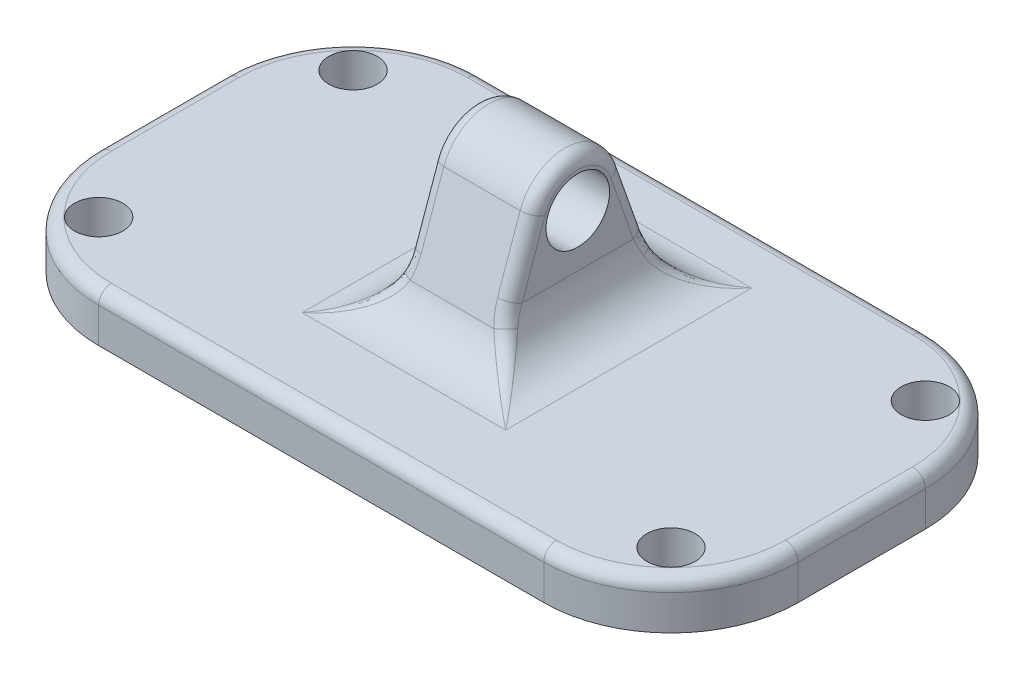
SolidWorks part; units mm, degrees
ref_plane "Front Plane" through (0, 0, 0) normal (0, 0, 1) x (1, 0, 0)
ref_plane "Top Plane" through (0, 0, 0) normal (0, 1, 0) x (1, 0, 0)
ref_plane "Right Plane" through (0, 0, 0) normal (1, 0, 0) x (0, 0, -1)
sketch "Sketch1" plane through (0, 0, 0) normal (0, 1, 0) x (1, 0, 0)
  line L0 (-57.15, 25.4) -> (57.15, 25.4) construction
  line L1 (-69.85, 38.1) -> (69.85, 38.1)
  line L2 (-69.85, 38.1) -> (-69.85, -38.1)
  line L3 (-69.85, -38.1) -> (69.85, -38.1)
  line L4 (69.85, 38.1) -> (69.85, -38.1)
  line L5 (-69.85, 38.1) -> (69.85, -38.1) construction
  line L6 (-69.85, -38.1) -> (69.85, 38.1) construction
  line L7 (57.15, 25.4) -> (57.15, -25.4) construction
  line L8 (-57.15, -25.4) -> (57.15, -25.4) construction
  line L9 (-57.15, 25.4) -> (-57.15, -25.4) construction
  circle A0 centre (-57.15, -25.4) radius 4.826
  circle A1 centre (57.15, 25.4) radius 4.826
  circle A2 centre (57.15, -25.4) radius 4.826
  circle A3 centre (-57.15, 25.4) radius 4.826
  point P0 (0, 0)
  dimension "D4" = 9.652
  dimension "D1" = 139.7
  dimension "D2" = 76.2
  dimension "D3" = 12.7
extrude "Boss-Extrude1" add sketch "Sketch1" along normal mid plane 9.525
sketch "Sketch2" plane through (0, 0, 0) normal (1, 0, 0) x (0, 0, -1)
  line L0 (2.9826, 25.4) -> (2.9826, 13.97) construction
  line L1 (-16.0674, 0) -> (22.0326, 0)
  line L2 (-6.001, 28.5658) -> (-16.0674, 0)
  line L3 (11.9661, 28.5658) -> (22.0326, 0)
  arc A0 (11.9661, 28.5658) -> (-6.001, 28.5658) centre (2.9826, 25.4) ccw
  circle A1 centre (2.9826, 25.4) radius 6.35
  point P6 (2.9826, 0)
  dimension "D1" = 25.4
  dimension "D3" = 19.05
  dimension "D4" = 12.7
  dimension "D2" = 38.1
extrude "Boss-Extrude2" add sketch "Sketch2" along normal mid plane 20.32
fillet "Fillet1" radius 25.4 4 edges at (-69.85, 0, 38.1) (-69.85, 0, -38.1) (69.85, 0, 38.1) (69.85, 0, -38.1)
fillet "Fillet2" radius 10.16 4 edges at (0, 4.7625, -20.3543) (-10.16, 4.7625, -2.9826) (0, 4.7625, 14.3892) (10.16, 4.7625, -2.9826)
fillet "Fillet3" radius 2.54 8 edges at (-62.4105, 4.7625, 30.6605) (-69.85, 4.7625, 0) (-62.4105, 4.7625, -30.6605) (0, 4.7625, -38.1) (62.4105, 4.7625, -30.6605) (69.85, 4.7625, 0) (62.4105, 4.7625, 30.6605) (0, 4.7625, 38.1)
fillet "Fillet6" radius 2.54 14 edges at (14.4499, 6.6299, -21.6762) (10.3054, 13.2096, -17.3775) (10.16, 21.7441, -14.37) (14.4499, 6.6299, 15.7111) (10.3054, 13.2096, 11.4124) (10.16, 21.7441, 8.4049) (-14.4499, 6.6299, -21.6762) (-10.3054, 13.2096, -17.3775) (-10.16, 21.7441, -14.37) (-14.4499, 6.6299, 15.7111) (-10.3054, 13.2096, 11.4124) (-10.16, 21.7441, 8.4049) (10.16, 34.925, -2.9826) (-10.16, 34.925, -2.9826)
equation "\"0.5n\"=0.1"
